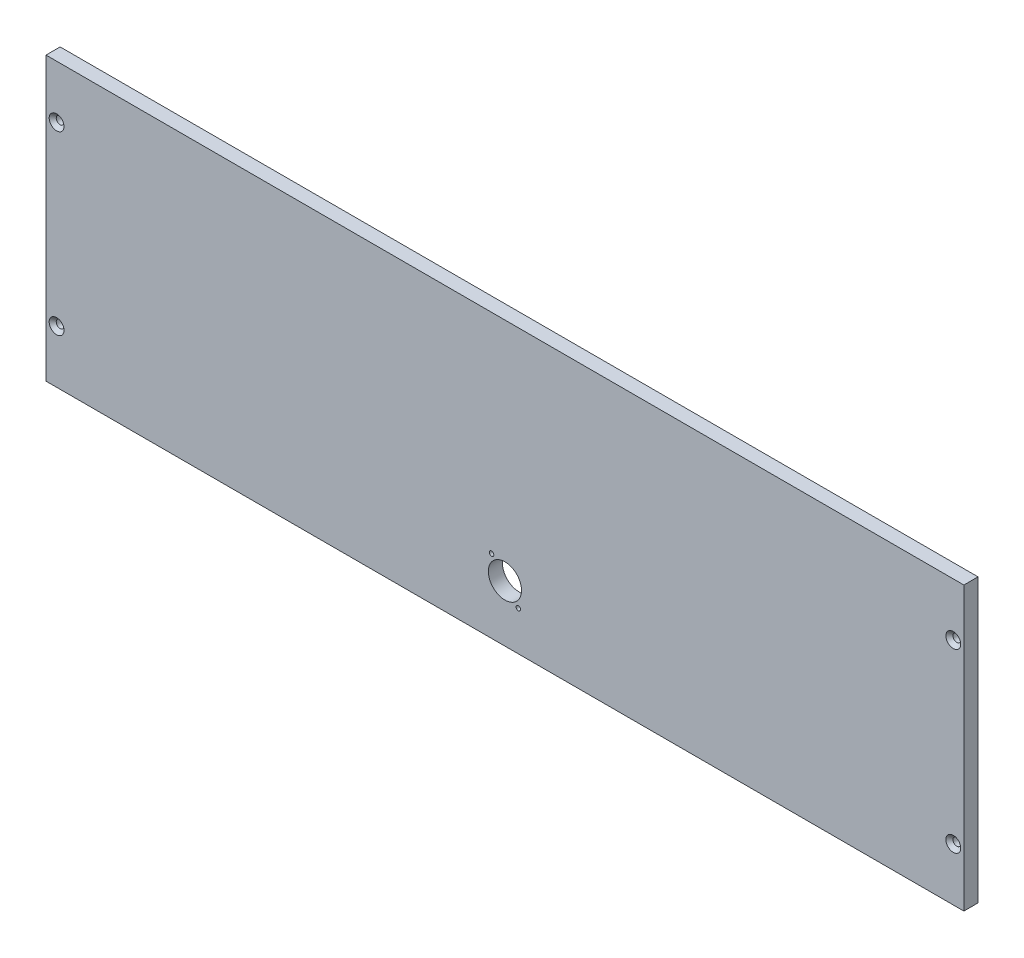
SolidWorks part; units mm, degrees
ref_plane "Plan de face" through (0, 0, 0) normal (0, 0, 1) x (1, 0, 0)
ref_plane "Plan de dessus" through (0, 0, 0) normal (0, 1, 0) x (1, 0, 0)
ref_plane "Plan de droite" through (0, 0, 0) normal (1, 0, 0) x (0, 0, -1)
sketch "Esquisse1" plane through (0, 0, 0) normal (0, 0, 1) x (1, 0, 0)
  line L1 (0, 0) -> (650, 0)
  line L2 (0, 0) -> (0, 200)
  line L3 (0, 200) -> (650, 200)
  line L4 (650, 0) -> (650, 200)
  dimension "D1" = 200
  dimension "D2" = 650
extrude "Boss.-Extru.1" add sketch "Esquisse1" along normal blind 10
sketch "Esquisse2" plane through (0, 0, 10) normal (0, 0, 1) x (1, 0, 0)
  line L0 (0, 200) -> (0, 0) construction
  line L1 (650, 200) -> (0, 200) construction
  line L2 (0, 0) -> (650, 0) construction
  line L3 (650, 0) -> (650, 200) construction
  circle A0 centre (7.5, 162.5) radius 2.75
  circle A1 centre (642.5, 162.5) radius 2.75
  circle A2 centre (7.5, 37.5) radius 2.75
  circle A3 centre (642.5, 37.5) radius 2.75
  dimension "D1" = 5.5
  dimension "D2" = 5.5
  dimension "D3" = 5.5
  dimension "D4" = 5.5
  dimension "D5" = 7.5
  dimension "D6" = 7.5
  dimension "D7" = 37.5
  dimension "D8" = 37.5
  dimension "D9" = 37.5
  dimension "D10" = 37.5
  dimension "D11" = 7.5
  dimension "D12" = 7.5
extrude "Enlèv. mat.-Extru.1" cut sketch "Esquisse2" against normal blind 10
chamfer "Chanfrein1" distance 2.5 angle 45 4 edges at (10.25, 162.5, 10) (10.25, 37.5, 10) (645.25, 37.5, 10) (645.25, 162.5, 10)
sketch "Esquisse3" plane through (0, 0, 10) normal (0, 0, 1) x (1, 0, 0)
  line L0 (0, 0) -> (650, 0) construction
  line L1 (334.5004, 28.0006) -> (325, 40)
  line L2 (325, 40) -> (315.4996, 51.9994)
  line L3 (325, 40) -> (265.8175, 40)
  line L4 (325, 40) -> (364.3682, 40)
  circle A0 centre (325, 40) radius 11.75
  circle A1 centre (315.4996, 51.9994) radius 1.6
  circle A2 centre (334.5004, 28.0006) radius 1.6
  point P4 (325, 0)
  dimension "D1" = 23.5
  dimension "D4" = 3.2
  dimension "D5" = 3.2
  dimension "D2" = 0
  dimension "D3" = 40
  dimension "D6" = 30.61
  dimension "D7" = 15.305
  dimension "D8" = 51.63
  dimension "D9" = 180
  dimension "D10" = 51.63
  dimension "D11" = 15.305
extrude "Enlèv. mat.-Extru.2" cut sketch "Esquisse3" against normal blind 10 contours L3 A0 L1 | L4 A0 L2 | L1 A0 L4 | L2 A0 L3 | A1 | A2 region at (314.1, 52.6764, 10) region at (322.2589, 34.3335, 10) region at (331.8154, 36.7031, 10) region at (335.1774, 29.4002, 10) region at (318.1846, 43.2969, 10) region at (327.7411, 45.6665, 10)
